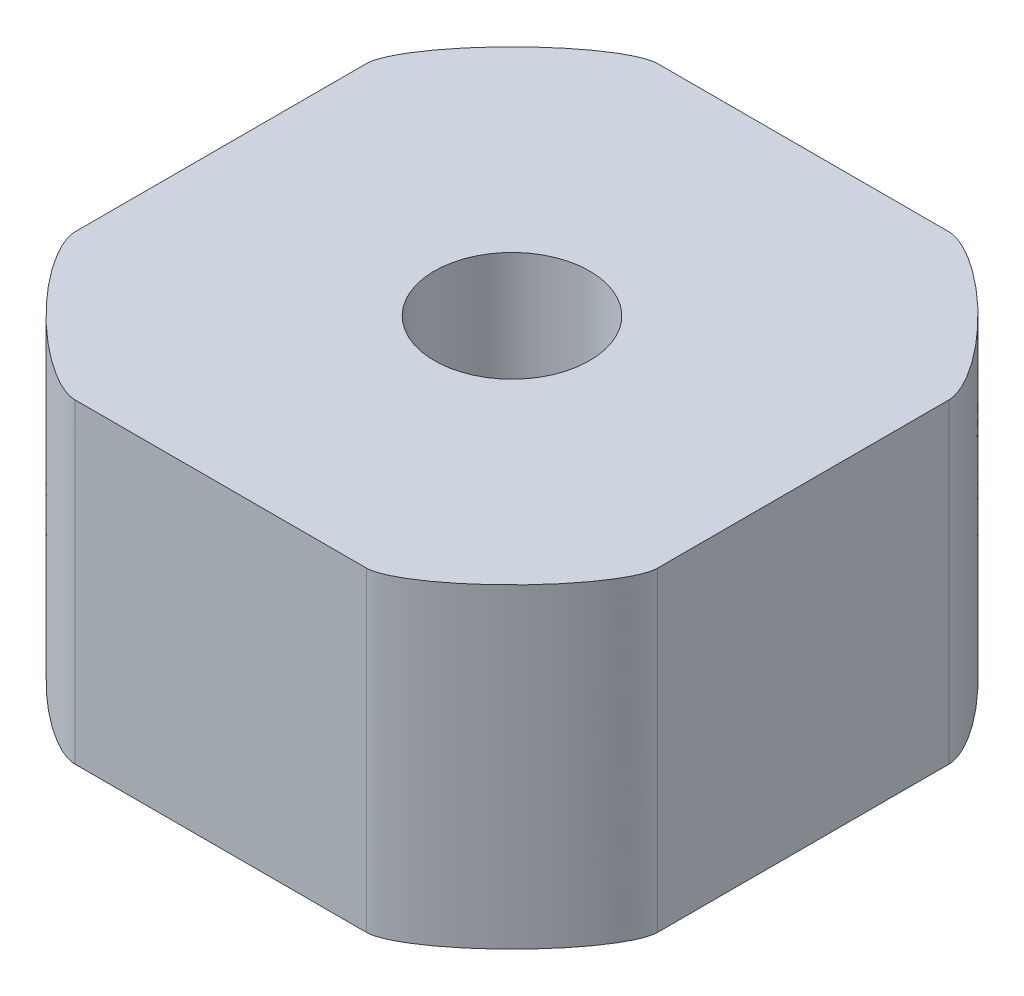
SolidWorks part; units mm, degrees
ref_plane "Ebene vorne" through (0, 0, 0) normal (0, 0, 1) x (1, 0, 0)
ref_plane "Ebene oben" through (0, 0, 0) normal (0, 1, 0) x (1, 0, 0)
ref_plane "Ebene rechts" through (0, 0, 0) normal (1, 0, 0) x (0, 0, -1)
sketch "Sketch4" plane through (0, 0, 0) normal (0, 1, 0) x (1, 0, 0)
  line L0 (0, 0) -> (0, 6) construction
  line L1 (-6, -6) -> (6, -6)
  line L2 (-6, -6) -> (-6, 6)
  line L3 (-6, 6) -> (6, 6)
  line L4 (6, -6) -> (6, 6)
  line L5 (0, 0) -> (-6, 0) construction
  dimension "D1" = 12
  dimension "D2" = 12
extrude "Boss-Extrude2" add sketch "Sketch4" along normal blind 6.5
sketch "Sketch3" plane through (0, 0, 0) normal (0, -1, 0) x (1, 0, 0)
  line L1 (1.6386, -2.9203) -> (3.3484, -0.0411)
  line L2 (3.3484, -0.0411) -> (1.7098, 2.8792)
  line L3 (1.7098, 2.8792) -> (-1.6386, 2.9203)
  line L4 (-1.6386, 2.9203) -> (-3.3484, 0.0411)
  line L5 (-3.3484, 0.0411) -> (-1.7098, -2.8792)
  line L6 (-1.7098, -2.8792) -> (1.6386, -2.9203)
  circle A0 centre (0, 0) radius 2.9 construction
  dimension "D1" = 5.8
extrude "Cut-Extrude1" cut sketch "Sketch3" against normal blind 3 contours L6 L1 L2 L3 L4 L5
sketch "Sketch5" plane through (0, 0, 0) normal (0, -1, 0) x (1, 0, 0)
  circle A0 centre (0, 0) radius 1.6
  dimension "D1" = 3.2
extrude "Cut-Extrude2" cut sketch "Sketch5" against normal through all both and the other way through all
fillet "Fillet1" radius 3 1 edges at (-6, 3.25, 6) conic rho 0.2
fillet "Fillet2" radius 3 1 edges at (-6, 3.25, -6) conic rho 0.2
fillet "Fillet3" radius 3 1 edges at (6, 3.25, 6) conic rho 0.2
fillet "Fillet4" radius 3 1 edges at (6, 3.25, -6) conic rho 0.2
